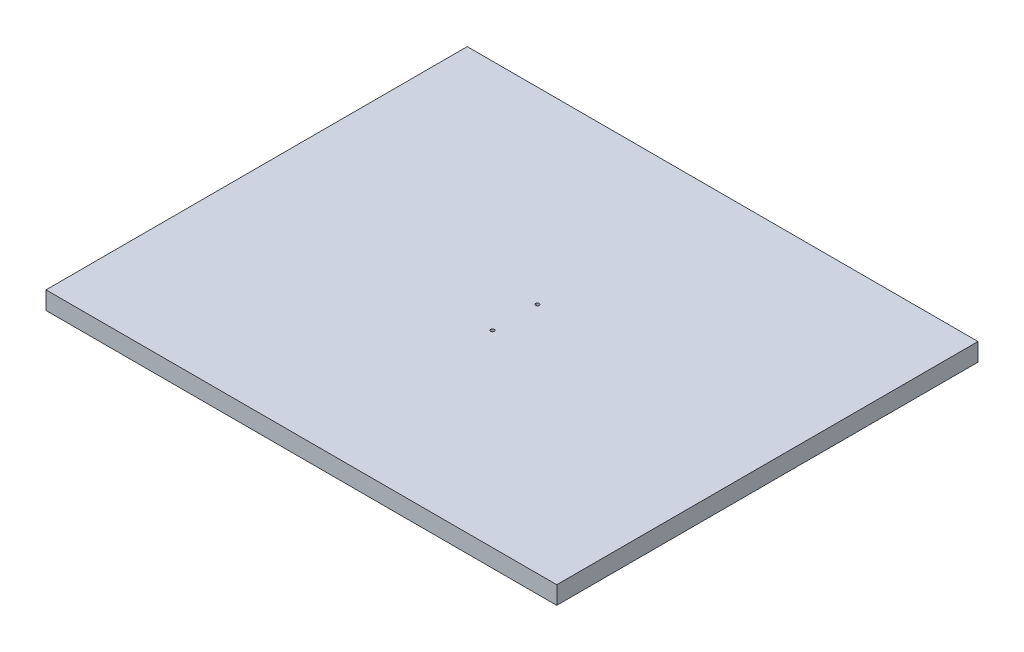
SolidWorks part; units mm, degrees
ref_plane "Alzado" through (0, 0, 0) normal (0, 0, 1) x (1, 0, 0)
ref_plane "Planta" through (0, 0, 0) normal (0, 1, 0) x (1, 0, 0)
ref_plane "Vista lateral" through (0, 0, 0) normal (1, 0, 0) x (0, 0, -1)
sketch "Croquis1" plane through (0, 0, 0) normal (0, 1, 0) x (1, 0, 0)
  line L0 (0, -176.5) -> (0, 176.5) construction
  line L1 (-214, -176.5) -> (214, -176.5)
  line L2 (-214, -176.5) -> (-214, 176.5)
  line L3 (-214, 176.5) -> (214, 176.5)
  line L4 (214, -176.5) -> (214, 176.5)
  line L5 (-214, -176.5) -> (214, 176.5) construction
  line L6 (-214, 176.5) -> (214, -176.5) construction
  circle A2 centre (2.5, 18.8) radius 1.5
  circle A3 centre (2.5, -18.8) radius 1.5
  point P0 (0, 0)
  dimension "D6" = 3
  dimension "D1" = 428
  dimension "D2" = 353
  dimension "D7" = 2.5
  dimension "D8" = 18.8
  dimension "D9" = 18.8
extrude "Saliente-Extruir1" add sketch "Croquis1" along normal blind 15
sketch "Croquis2" plane through (0, 15, 0) normal (0, 1, 0) x (1, 0, 0)
  line L0 (0, 176.5) -> (0, -176.5) construction
  line L1 (214, 176.5) -> (-214, 176.5) construction
  line L2 (-214, -176.5) -> (214, -176.5) construction
  line L3 (-176.5, 176.5) -> (-176.5, -176.5) construction
  line L4 (176.5, 176.5) -> (176.5, -176.5) construction
  dimension "D1" = 176.5
  dimension "D2" = 176.5
